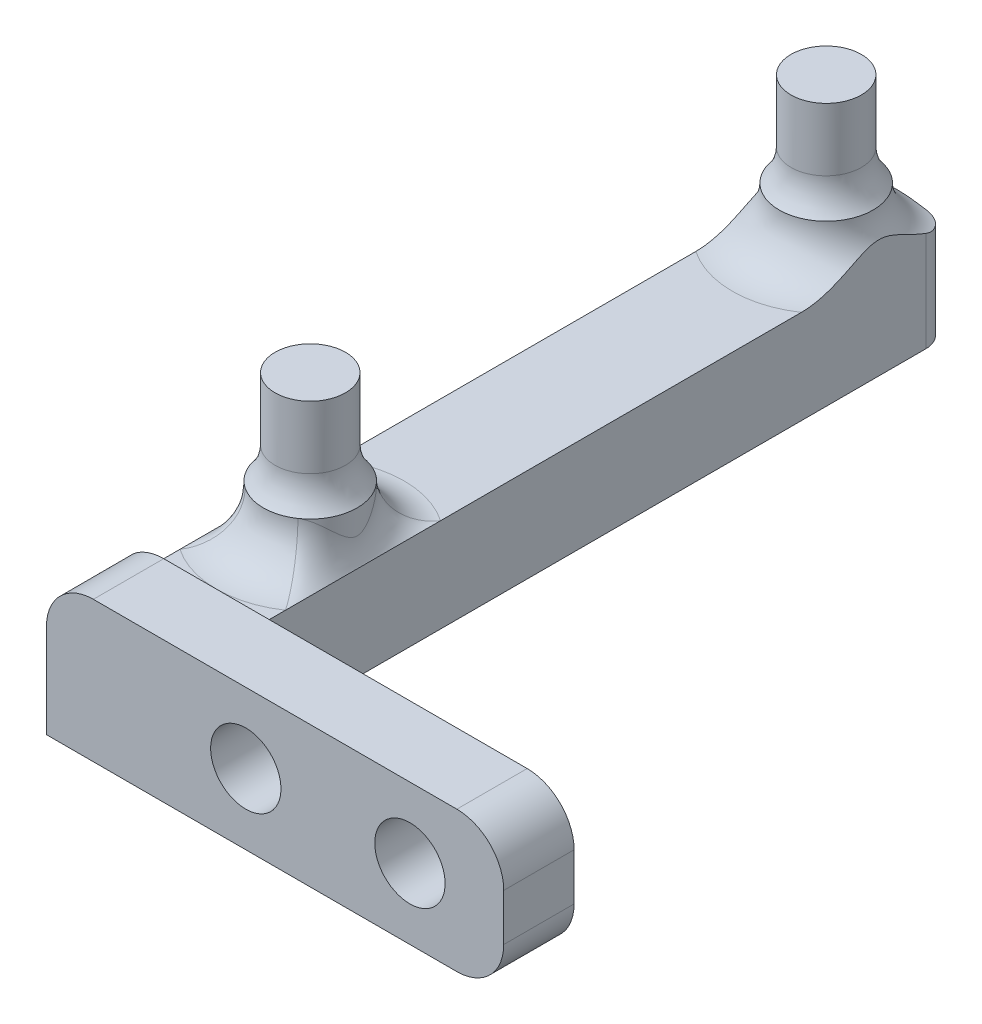
SolidWorks part; units mm, degrees
ref_plane "Front Plane" through (0, 0, 0) normal (0, 0, 1) x (1, 0, 0)
ref_plane "Top Plane" through (0, 0, 0) normal (0, 1, 0) x (1, 0, 0)
ref_plane "Right Plane" through (0, 0, 0) normal (1, 0, 0) x (0, 0, -1)
sketch "Sketch1" plane through (0, 0, 0) normal (0, 1, 0) x (1, 0, 0)
  line L0 (0, 0) -> (0, 15.9628) construction
  line L2 (-2.25, 19.3926) -> (2.25, 19.3926)
  line L3 (-2.25, 19.3926) -> (-2.25, -8.6074)
  line L4 (-2.25, -8.6074) -> (2.25, -8.6074)
  line L5 (2.25, 19.3926) -> (2.25, -8.6074)
  line L6 (-2.25, -8.6074) -> (2.25, -8.6074)
  line L7 (-2.25, -8.6074) -> (-2.25, -14.6074)
  line L8 (-2.25, -14.6074) -> (2.25, -14.6074)
  line L9 (2.25, -8.6074) -> (2.25, -14.6074)
  circle A0 centre (0, 16.3926) radius 2
  circle A1 centre (0, -5.6074) radius 2
  dimension "D1" = 2.25
  dimension "D3" = 4
  dimension "D4" = 4
  dimension "D5" = 3
  dimension "D6" = 3
  dimension "D7" = 22
  dimension "D2" = 4.5
  dimension "D8" = 6
extrude "Boss-Extrude1" add sketch "Sketch1" along normal blind 4 contours L9 L4 L7 L8 | A0 L2 L3 L4 L5 A1 region at (0, 0, -5.3926) region at (0, 0, 11.6074)
extrude "Boss-Extrude2" add sketch "Sketch1<3>" along normal blind 6 contours A1 | A0 L0 | L0 A0 region at (0, 0, -16.3926) region at (0, 0, 5.6074)
sketch "Sketch1<3>" plane through (0, 0, 0) normal (0, 1, 0) x (1, 0, 0) same geometry as "Sketch1"
sketch "Sketch2" plane through (0, 6, 0) normal (0, 1, 0) x (1, 0, 0)
  circle A0 centre (0, 16.3926) radius 1.5
  circle A1 centre (0, -5.6074) radius 1.5
  dimension "D1" = 3
  dimension "D2" = 3
extrude "Boss-Extrude3" add sketch "Sketch2" along normal blind 4
fillet "Fillet1" radius 2 1 edges at (0, 6, 7.1074)
fillet "Fillet2" radius 2 1 edges at (0, 6, -14.8926)
fillet "Fillet3" radius 2 1 edges at (0, 4, 7.6074)
fillet "Fillet4" radius 2 1 edges at (0, 4, -14.3926)
sketch "Sketch3" plane through (2.25, 0, 0) normal (1, 0, 0) x (0, 0, -1)
  line L0 (19.3926, 0) -> (-14.6074, 0) construction
  line L1 (-14.6074, 4) -> (-11.6074, 4)
  line L2 (-14.6074, 4) -> (-14.6074, 0)
  line L3 (-14.6074, 0) -> (-11.6074, 0)
  line L4 (-11.6074, 4) -> (-11.6074, 0)
  dimension "D1" = 3
extrude "Boss-Extrude4" add sketch "Sketch3" along normal blind 15
sketch "Sketch5" plane through (0, 4, 0) normal (0, 1, 0) x (1, 0, 0)
  line L0 (-2.25, -14.6074) -> (17.25, -14.6074) construction
  line L1 (-2.25, -14.6074) -> (2.25, -14.6074)
  line L2 (-2.25, -14.6074) -> (-2.25, -11.6074)
  line L3 (-2.25, -11.6074) -> (2.25, -11.6074)
  line L4 (2.25, -14.6074) -> (2.25, -11.6074)
extrude "Boss-Extrude5" add sketch "Sketch5" along normal blind 2
sketch "Sketch7" plane through (2.25, 0, 0) normal (1, 0, 0) x (0, 0, -1)
  line L1 (-11.6074, 6) -> (-14.6074, 6)
  line L2 (-11.6074, 6) -> (-11.6074, 4)
  line L3 (-11.6074, 4) -> (-14.6074, 4)
  line L4 (-14.6074, 6) -> (-14.6074, 4)
extrude "Boss-Extrude6" add sketch "Sketch7" along normal up to surface (15 mm away) up to face at (17.25, 2, 13.1074)
sketch "Sketch8" plane through (0, 0, 11.6074) normal (0, 0, -1) x (-1, 0, 0)
  line L0 (-17.25, 3) -> (4.7513, 3) construction
  line L1 (-17.25, 0) -> (-17.25, 6) construction
  line L2 (-2.25, 0) -> (-2.25, 4) construction
  circle A0 centre (-6.25, 3) radius 1.5
  circle A1 centre (-13.25, 3) radius 1.5
  dimension "D1" = 3
  dimension "D2" = 3
  dimension "D3" = 4
  dimension "D4" = 4
extrude "Cut-Extrude1" cut sketch "Sketch8" against normal through all
fillet "Fillet12" radius 2 2 edges at (2.25, 2, 11.6074) (0, 4, 11.6074)
fillet "Fillet13" radius 2 1 edges at (-2.25, 6, 13.1074)
fillet "Fillet14" radius 2 2 edges at (17.25, 6, 13.1074) (17.25, 0, 13.1074)
fillet "Fillet16" radius 1 2 edges at (-2.25, 2.0078, -19.3926) (2.25, 2.0078, -19.3926)
